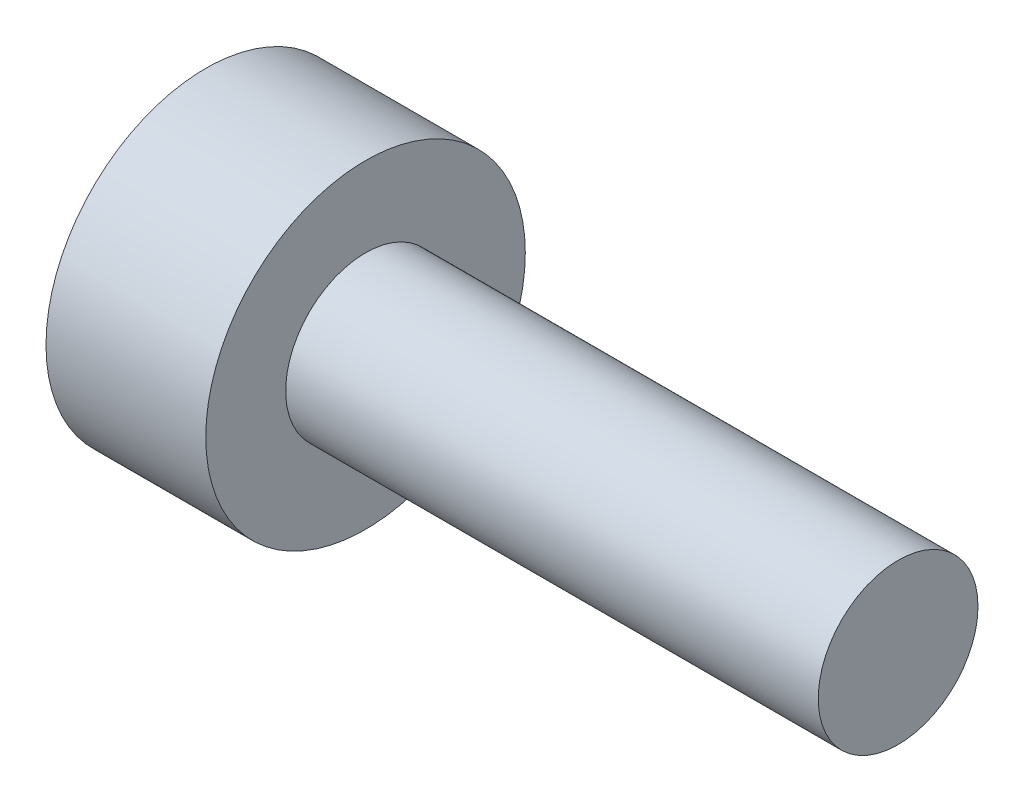
SolidWorks part; units mm, degrees
material "AISI 1045 Steel, cold drawn"
ref_plane "前视基准面" through (0, 0, 0) normal (0, 0, 1) x (1, 0, 0)
ref_plane "上视基准面" through (0, 0, 0) normal (0, 1, 0) x (1, 0, 0)
ref_plane "右视基准面" through (0, 0, 0) normal (1, 0, 0) x (0, 0, -1)
sketch "Sketch1" plane through (0, 0, 0) normal (1, 0, 0) x (0, 0, -1)
  circle A0 centre (0, 0) radius 3
  dimension "D1" = 6
extrude "Boss-Extrude1" add sketch "Sketch1" along normal blind 3
sketch "Sketch2" plane through (3, 0, 0) normal (1, 0, 0) x (0, 0, -1)
  circle A0 centre (0, 0) radius 1.5
  dimension "D1" = 3
extrude "Boss-Extrude2" add sketch "Sketch2" along normal blind 10
